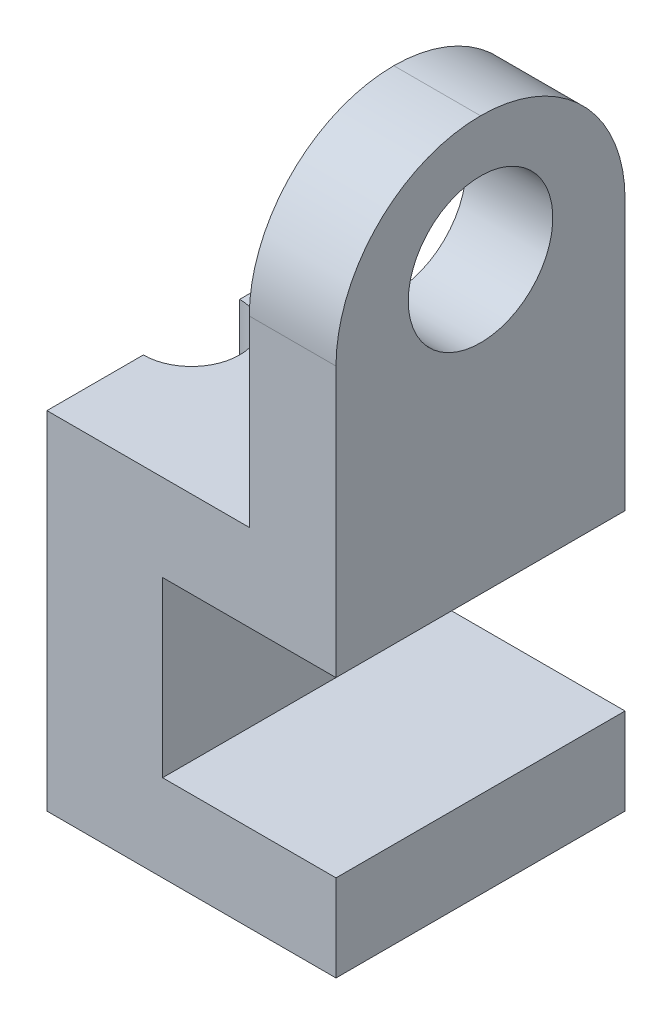
SolidWorks part; units mm, degrees
ref_plane "Ön Düzlem" through (0, 0, 0) normal (0, 0, 1) x (1, 0, 0)
ref_plane "Üst Düzlem" through (0, 0, 0) normal (0, 1, 0) x (1, 0, 0)
ref_plane "Sağ Düzlem" through (0, 0, 0) normal (1, 0, 0) x (0, 0, -1)
sketch "Çizim1" plane through (0, 0, 0) normal (0, 1, 0) x (1, 0, 0)
  line L1 (-1.2676, 0) -> (28.7324, 0)
  line L2 (-1.2676, 0) -> (-1.2676, 30)
  line L3 (-1.2676, 30) -> (28.7324, 30)
  line L4 (28.7324, 0) -> (28.7324, 30)
  dimension "D1" = 30
  dimension "D2" = 30
extrude "Yükseklik-Ekstrüzyon1" add sketch "Çizim1" along normal blind 36
sketch "Çizim3" plane through (0, 0, 0) normal (0, 0, 1) x (1, 0, 0)
  line L3 (28.7324, 9) -> (10.7324, 9)
  line L4 (28.7324, 9) -> (28.7324, 27)
  line L5 (28.7324, 27) -> (10.7324, 27)
  line L6 (10.7324, 9) -> (10.7324, 27)
  point P4 (21.5591, 18)
extrude "Kes-Ekstrüzyon2" cut sketch "Çizim3" against normal through all
sketch "Çizim5" plane through (0, 36, 0) normal (0, 1, 0) x (1, 0, 0)
  line L0 (-1.2676, 30) -> (-1.2676, 0) construction
  circle A1 centre (-1.2676, 15) radius 5
  dimension "D1" = 10
extrude "Kes-Ekstrüzyon3" cut sketch "Çizim5" against normal through all
sketch "Çizim6" plane through (0, 36, 0) normal (0, 1, 0) x (1, 0, 0)
  line L1 (28.7324, 30) -> (19.7324, 30)
  line L2 (28.7324, 30) -> (28.7324, 0)
  line L3 (28.7324, 0) -> (19.7324, 0)
  line L4 (19.7324, 30) -> (19.7324, 0)
  dimension "D1" = 9
extrude "Yükseklik-Ekstrüzyon2" add sketch "Çizim6" along normal blind 34
fillet "Radyus1" radius 15 2 edges at (24.2324, 70, 0) (24.2324, 70, -30)
sketch "Çizim7" plane through (19.7324, 0, 0) normal (-1, 0, 0) x (0, 0, 1)
  circle A0 centre (-15, 57.0878) radius 7.5
  dimension "D1" = 15
extrude "Kes-Ekstrüzyon4" cut sketch "Çizim7" against normal through all
